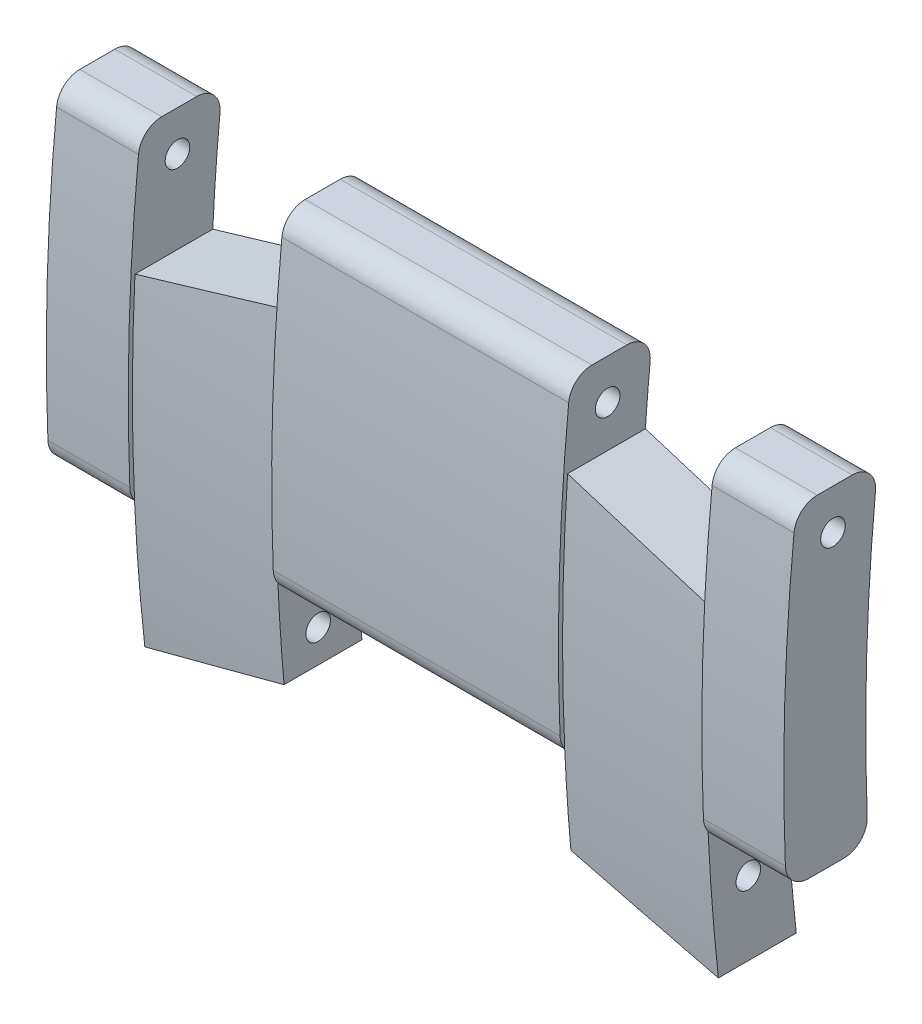
SolidWorks part; units mm, degrees
ref_plane "Front Plane" through (0, 0, 0) normal (0, 0, 1) x (1, 0, 0)
ref_plane "Top Plane" through (0, 0, 0) normal (0, 1, 0) x (1, 0, 0)
ref_plane "Right Plane" through (0, 0, 0) normal (1, 0, 0) x (0, 0, -1)
sketch "Sketch1" plane through (0, 0, 0) normal (0, 0, 1) x (1, 0, 0)
  line L0 (0, 0) -> (0, 8)
  line L1 (0, 8) -> (2, 8)
  line L2 (2, 8) -> (2, 5)
  line L3 (2, 5) -> (5.5, 6)
  line L4 (5.5, 6) -> (5.5, 8)
  line L5 (5.5, 8) -> (12.5, 8)
  line L6 (12.5, 8) -> (12.5, 6)
  line L7 (12.5, 6) -> (16, 5)
  line L8 (16, 5) -> (16, 8)
  line L9 (16, 8) -> (18, 8)
  line L10 (18, 8) -> (18, 0)
  line L11 (18, 0) -> (16, 0)
  line L12 (16, 0) -> (16, -3)
  line L13 (16, -3) -> (12.5, -2)
  line L14 (12.5, -2) -> (12.5, 0)
  line L15 (5.5, -2) -> (2, -3)
  line L16 (2, -3) -> (2, 0)
  line L17 (2, 0) -> (0, 0)
  line L18 (12.5, 0) -> (5.5, 0)
  line L19 (5.5, 0) -> (5.5, -2)
  dimension "D1" = 2
  dimension "D2" = 3.5
  dimension "D3" = 7
  dimension "D4" = 3.5
  dimension "D5" = 2
  dimension "D6" = 2
  dimension "D7" = 3.5
  dimension "D8" = 7
  dimension "D9" = 3.5
  dimension "D10" = 2
  dimension "D11" = 3
  dimension "D12" = 2
  dimension "D13" = 2
  dimension "D14" = 3
  dimension "D15" = 3
  dimension "D16" = 2
  dimension "D17" = 3
  dimension "D18" = 8
extrude "Boss-Extrude2" add sketch "Sketch1" along normal blind 5
sketch "Sketch8" plane through (0, 0, 0) normal (1, 0, 0) x (0, 0, -1)
  line L0 (0, 8) -> (0, 0) construction
  circle A0 centre (49, 2.5) radius 50
  dimension "D1" = 2.5
  dimension "D2" = 49
extrude "Cut-Extrude6" cut sketch "Sketch8" along normal blind 20
sketch "Sketch9" plane through (0, 0, 0) normal (1, 0, 0) x (0, 0, -1)
  circle A0 centre (47.1, 2.5) radius 50
  dimension "D1" = 2.5
  dimension "D2" = 47.1
extrude "Cut-Extrude7" cut sketch "Sketch9" along normal blind 20 flip side to cut
ref_plane "Plane1" through (0, 0, 4) normal (0, 0, 1) x (1, 0, 0)
sketch "Sketch11" plane through (0, 0, 4) normal (0, 0, 1) x (1, 0, 0)
  line L0 (0, 0) -> (0, 8)
  line L1 (0, 8) -> (2, 8)
  line L2 (2, 8) -> (2, 0)
  line L3 (2, 0) -> (0, 0)
  line L4 (5.5, 8) -> (12.5, 8)
  line L5 (12.5, 8) -> (12.5, 0)
  line L6 (12.5, 0) -> (5.5, 0)
  line L7 (5.5, 0) -> (5.5, 8)
  line L8 (16, 8) -> (18, 8)
  line L9 (18, 8) -> (18, 0)
  line L10 (18, 0) -> (16, 0)
  line L11 (16, 0) -> (16, 8)
extrude "Boss-Extrude4" add sketch "Sketch11" against normal blind 2
sketch "Sketch12" plane through (0, 0, 0) normal (1, 0, 0) x (0, 0, -1)
  circle A0 centre (47, 2.5) radius 50
  dimension "D1" = 2.5
  dimension "D2" = 47
extrude "Cut-Extrude8" cut sketch "Sketch12" along normal blind 20 flip side to cut
sketch "Sketch13" plane through (0, 0, 0) normal (1, 0, 0) x (0, 0, -1)
  line L0 (-2.6966, 8) -> (-0.6966, 8) construction
  circle A0 centre (-1.7993, 7.02) radius 0.3
  arc A1 (-0.6966, 8) -> (-0.9375, 0) centre (49, 2.5) ccw construction
  dimension "D1" = 0.98
  dimension "D2" = 51
extrude "Cut-Extrude10" cut sketch "Sketch13" along normal through all
sketch "Sketch14" plane through (0, 0, 0) normal (1, 0, 0) x (0, 0, -1)
  line L0 (-2.5966, -3) -> (-0.6966, -3) construction
  circle A0 centre (-1.8656, -1.2) radius 0.3
  arc A1 (-0.9375, 0) -> (-0.6966, -3) centre (49, 2.5) ccw construction
  dimension "D1" = 1.8
  dimension "D2" = 51
extrude "Cut-Extrude11" cut sketch "Sketch14" along normal blind 20
fillet "Fillet1" radius 0.57 12 edges at (17, 0, 0.9375) (17, 0, 2.9375) (9, 0, 0.9375) (9, 0, 2.9375) (1, 0, 0.9375) (1, 0, 2.9375) (17, 8, 2.6966) (17, 8, 0.6966) (9, 8, 2.6966) (1, 8, 2.6966) (1, 8, 0.6966) (9, 8, 0.6966)
